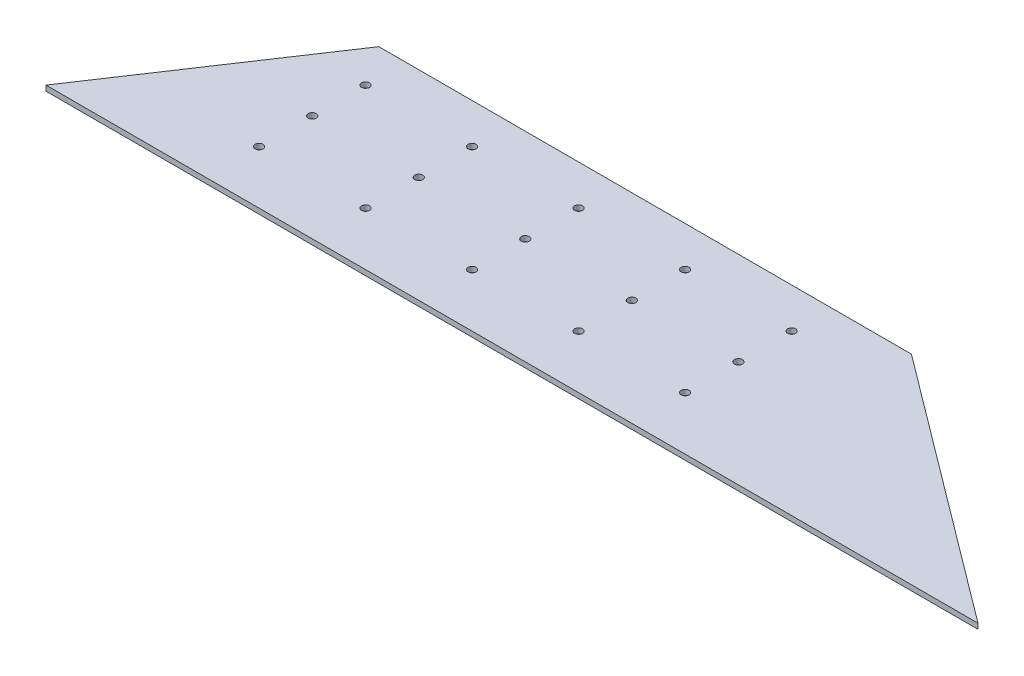
SolidWorks part; units mm, degrees
ref_plane "Front Plane" through (0, 0, 0) normal (0, 0, 1) x (1, 0, 0)
ref_plane "Top Plane" through (0, 0, 0) normal (0, 1, 0) x (1, 0, 0)
ref_plane "Right Plane" through (0, 0, 0) normal (1, 0, 0) x (0, 0, -1)
sketch "Sketch1" plane through (0, 0, 0) normal (0, 1, 0) x (1, 0, 0)
  line L0 (-17.984, 0) -> (332.016, 0)
  line L1 (-266.7276, 0) -> (266.7276, 0) construction
  line L2 (332.016, 0) -> (232.016, 75)
  line L3 (232.016, 75) -> (32.016, 75)
  line L4 (32.016, 75) -> (-17.984, 0)
  line L5 (-45.5557, 20) -> (439.4037, 20) construction
  line L6 (-34.9172, 40) -> (434.9926, 40) construction
  line L7 (-27.9699, 60) -> (319.174, 60) construction
  circle A0 centre (42.016, 20) radius 1.5
  circle A1 centre (82.016, 20) radius 1.5
  circle A2 centre (122.016, 20) radius 1.5
  circle A3 centre (162.016, 20) radius 1.5
  circle A4 centre (202.016, 20) radius 1.5
  circle A5 centre (42.016, 40) radius 1.5
  circle A6 centre (82.016, 40) radius 1.5
  circle A7 centre (122.016, 40) radius 1.5
  circle A8 centre (162.016, 40) radius 1.5
  circle A9 centre (202.016, 40) radius 1.5
  circle A10 centre (202.016, 60) radius 1.5
  circle A11 centre (162.016, 60) radius 1.5
  circle A12 centre (122.016, 60) radius 1.5
  circle A13 centre (82.016, 60) radius 1.5
  circle A14 centre (42.016, 60) radius 1.5
  dimension "D13" = 3
  dimension "D14" = 3
  dimension "D15" = 3
  dimension "D16" = 3
  dimension "D17" = 3
  dimension "D18" = 3
  dimension "D19" = 3
  dimension "D20" = 3
  dimension "D21" = 3
  dimension "D22" = 3
  dimension "D23" = 3
  dimension "D24" = 3
  dimension "D25" = 3
  dimension "D26" = 3
  dimension "D27" = 3
  dimension "D1" = 350
  dimension "D2" = 75
  dimension "D3" = 100
  dimension "D4" = 200
  dimension "D5" = 20
  dimension "D6" = 40
  dimension "D7" = 60
  dimension "D8" = 60
  dimension "D9" = 100
  dimension "D10" = 140
  dimension "D11" = 180
  dimension "D12" = 220
extrude "Boss-Extrude1" add sketch "Sketch1" along normal blind 2
